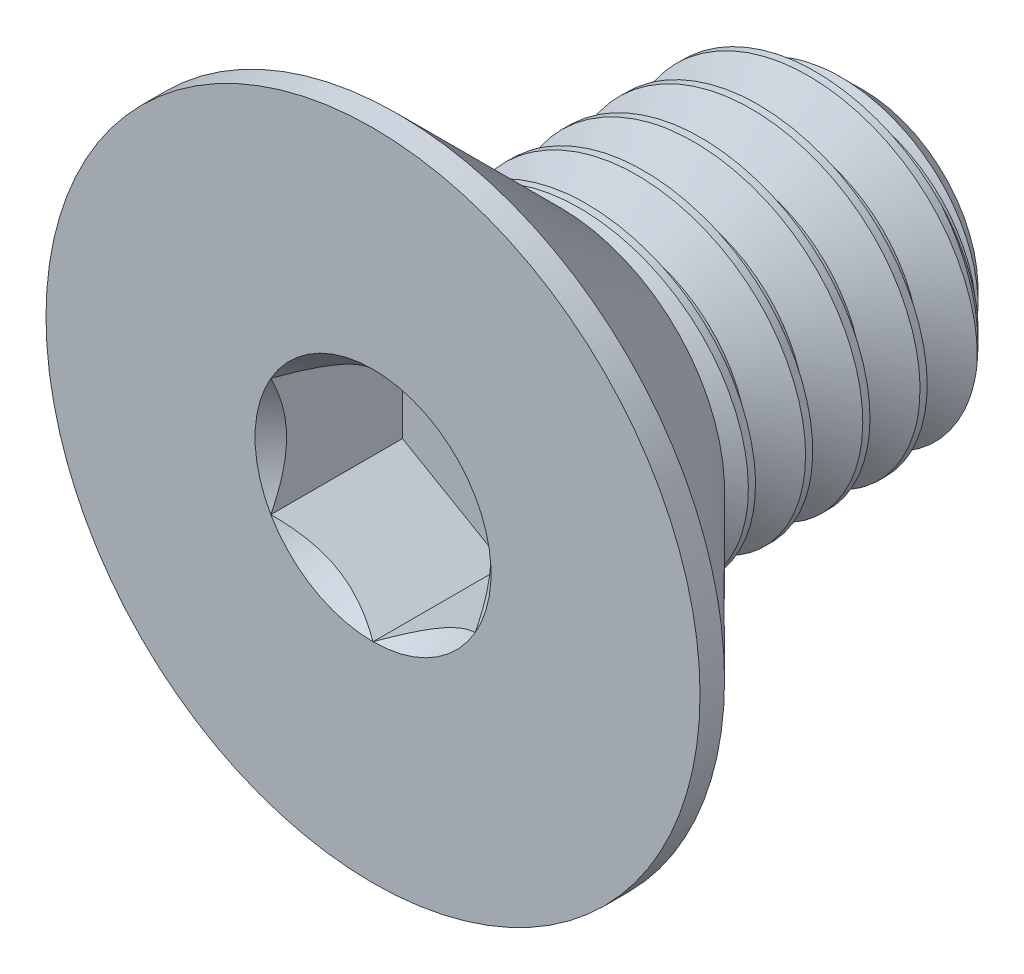
SolidWorks part; units mm, degrees
ref_plane "Front" through (0, 0, 0) normal (0, 0, 1) x (1, 0, 0)
ref_plane "Top" through (0, 0, 0) normal (0, 1, 0) x (1, 0, 0)
ref_plane "Right" through (0, 0, 0) normal (1, 0, 0) x (0, 0, -1)
sketch "Sketch1" plane through (0, 0, 0) normal (1, 0, 0) x (0, 0, -1)
  line L0 (-3, 4) -> (-2.7, 4) construction
  line L1 (-2.7, 4) -> (-0.7, 2) construction
  line L2 (-3, 2) -> (3, 2) construction
  line L3 (3, 2) -> (3, 0) construction
  line L4 (3, 0) -> (-3, 0) construction
  line L5 (-3, 0) -> (-3, 4) construction
  line L6 (-3, 4) -> (-3, -4) construction
  line L7 (3, 2) -> (3, -2) construction
  line L8 (-3, -4) -> (-2.7, -4) construction
  line L9 (-2.7, -4) -> (-0.7, -2) construction
  line L11 (-3, 2) -> (-3, 0) construction
  line L12 (-0.7, 2) -> (-0.7, 0) construction
  line L13 (2.9563, 2.0758) -> (3.3063, 1.4696) construction
  line L14 (3.3063, 1.4696) -> (3.6562, 2.0758) construction
  line L15 (3.6562, 2.0758) -> (2.9563, 2.0758) construction
  line L16 (3.3063, 2.0758) -> (3.3063, 2) construction
  line L17 (3.3063, 2) -> (3.3063, 1.5453) construction
  line L18 (3.3063, 1.5453) -> (3.3063, 1.4696) construction
  line L19 (3.3063, 2.0379) -> (3.6344, 2.0379) construction
  line L20 (3.3063, 2.0379) -> (2.9781, 2.0379) construction
  line L21 (3, 2) -> (3.6125, 2) construction
  line L22 (3.2625, 1.5453) -> (3.35, 1.5453) construction
  line L23 (3, -2) -> (-0.7, -2) construction
  point P10 (1.25, -2)
  point P24 (-0.7, 2)
  point P30 (0, 0)
  dimension "Head Diameter" = 8
  dimension "Head Height" = 2.3
  dimension "Length" = 6
  dimension "Countersink Angle" = 90
  dimension "Thread Pitch" = 0.7
  dimension "D2" = 0.0875
  dimension "Minimum Thread Length" = 3.7
  dimension "Thread Size" = 4
  dimension "D1" = 1.75
sketch "Sketch2" plane through (0, 0, 0) normal (0, 0, 1) x (1, 0, 0)
  line L1 (0, 1.4434) -> (-1.25, 0.7217) construction
  line L2 (-1.25, 0.7217) -> (-1.25, -0.7217) construction
  line L3 (-1.25, -0.7217) -> (0, -1.4434) construction
  line L4 (0, -1.4434) -> (1.25, -0.7217) construction
  line L5 (1.25, -0.7217) -> (1.25, 0.7217) construction
  line L6 (1.25, 0.7217) -> (0, 1.4434) construction
  circle A0 centre (0, 0) radius 1.25 construction
  dimension "Drive Size" = 2.5
sketch "Sketch3" plane through (0, 0, 0) normal (1, 0, 0) x (0, 0, -1)
  line L0 (-3, 2) -> (3, 2)
  line L1 (3, 2) -> (3, 0)
  line L2 (3, 0) -> (-3, 0)
  line L3 (-3, 0) -> (-3, 2)
revolve "Revolve1" add sketch "Sketch3" angle 360 about L4
chamfer "Chamfer1" distance 0.6 angle 45 1 edges at (0, 2, -3)
sketch "Sketch6" plane through (0, 0, 0) normal (1, 0, 0) x (0, 0, -1)
  line L0 (-3, 4) -> (-2.7, 4)
  line L1 (-2.7, 4) -> (-0.7, 2)
  line L2 (-0.7, 2) -> (-0.7, 0)
  line L3 (-0.7, 0) -> (-3, 0)
  line L4 (-3, 0) -> (-3, 4)
revolve "Revolve2" add sketch "Sketch6" angle 360 about L4
sketch "Sketch8" plane through (0, 0, 3) normal (0, 0, 1) x (1, 0, 0)
  line L0 (0, 1.4434) -> (-1.25, 0.7217) construction
  line L1 (1.25, 0.7217) -> (0, 1.4434) construction
  line L2 (1.25, -0.7217) -> (1.25, 0.7217) construction
  line L3 (0, -1.4434) -> (1.25, -0.7217) construction
  line L4 (-1.25, 0.7217) -> (-1.25, -0.7217) construction
  line L5 (-1.25, -0.7217) -> (0, -1.4434) construction
  line L6 (0, 1.4434) -> (-1.25, 0.7217)
  line L7 (1.25, 0.7217) -> (0, 1.4434)
  line L8 (1.25, -0.7217) -> (1.25, 0.7217)
  line L9 (0, -1.4434) -> (1.25, -0.7217)
  line L10 (-1.25, 0.7217) -> (-1.25, -0.7217)
  line L11 (-1.25, -0.7217) -> (0, -1.4434)
extrude "Cut-Extrude1" cut sketch "Sketch8" against normal blind 1.61
sketch "Sketch9" plane through (0, 0, 3) normal (0, 0, 1) x (1, 0, 0)
  circle A0 centre (0, 0) radius 1.4434
extrude "Cut-Extrude2" cut sketch "Sketch9" against normal up to next (1.61 mm away) draft 45
ref_plane "Plane1" through (0, 0, 0.7) normal (0, 0, 1) x (1, 0, 0)
split "Split1" trim tools "Plane1" bodies to split 124 resulting bodies 126 127
sketch "Sketch4" plane through (0, 0, -3) normal (0, 0, -1) x (-1, 0, 0)
  circle A0 centre (0, 0) radius 2 construction
  circle A1 centre (0, 0) radius 2
curve "Helix/Spiral1" pitch 0.7 height 4.4 radius 2 centre (0, 0, -3) axis (0, 0, 1) start towards (0, 1, 0)
sketch "Sketch10" plane through (0, 0, 0) normal (1, 0, 0) x (0, 0, -1)
  line L0 (2.9781, 2.0379) -> (3.6344, 2.0379)
  line L1 (3.6344, 2.0379) -> (3.35, 1.5453)
  line L2 (3.35, 1.5453) -> (3.2625, 1.5453)
  line L3 (3.2625, 1.5453) -> (2.9781, 2.0379)
sweep "Cut-Sweep1" cut profiles "Sketch10" path "Helix/Spiral1"
equation "\"D2@Sketch1\" = \"Thread Pitch@Sketch1\" / 8"
equation "\"D4@Helix/Spiral1\"=\"Thread Pitch@Sketch1\""
equation "\"D3@Helix/Spiral1\"=\"Minimum Thread Length@Sketch1\"+\"Thread Pitch@Sketch1\""
equation "\"D1@Chamfer1\"=\"Thread Size@Sketch1\"*.15"
equation "\"D1@Cut-Extrude1\"=\"Head Height@Sketch1\"*.7"
equation "\"D1@Sketch1\"=\"Thread Pitch@Sketch1\"*2.5"
